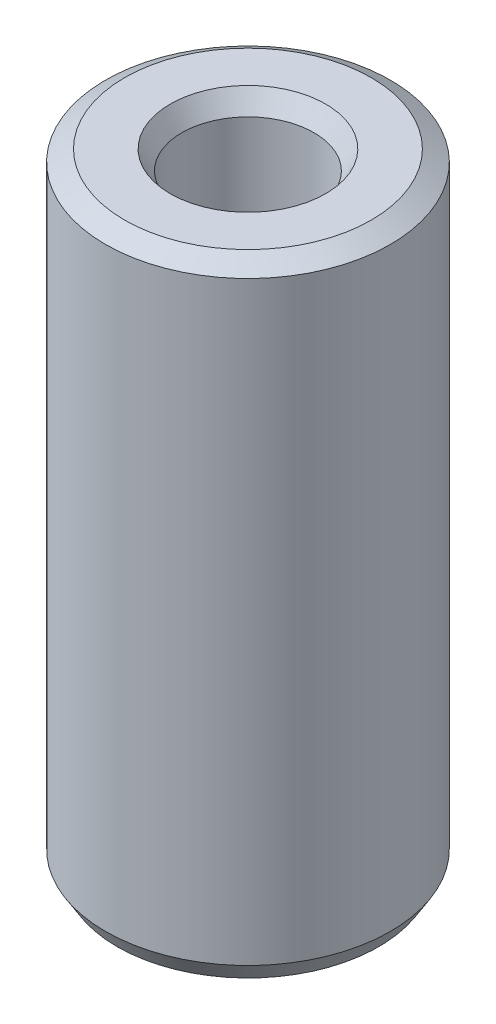
SolidWorks part; units mm, degrees
ref_plane "Front Plane" through (0, 0, 0) normal (0, 0, 1) x (1, 0, 0)
ref_plane "Top Plane" through (0, 0, 0) normal (0, 1, 0) x (1, 0, 0)
ref_plane "Right Plane" through (0, 0, 0) normal (1, 0, 0) x (0, 0, -1)
sketch "Sketch1" plane through (0, 0, 0) normal (0, 1, 0) x (1, 0, 0)
  circle A0 centre (0, 0) radius 47.5
  dimension "SLEEVE_OD" = 95
extrude "Boss-Extrude1" add sketch "Sketch1" along normal blind 208.6728
sketch "Sketch2" plane through (0, 0, 0) normal (0, 1, 0) x (1, 0, 0)
  circle A0 centre (0, 0) radius 22.0518
  dimension "BORE_D" = 44.1036
extrude "Cut-Extrude1" cut sketch "Sketch2" along normal through all
chamfer "Chamfer1" distance 3.8699 angle 58.631 4 edges at (0, 208.6728, 22.0518) (0, 0, 22.0518) (0, 0, 47.5) (0, 208.6728, 47.5) first distance on face at (0, 208.6728, 22.0518) first distance on face at (0, 0, 22.0518) first distance on face at (0, 208.6728, 47.5)
